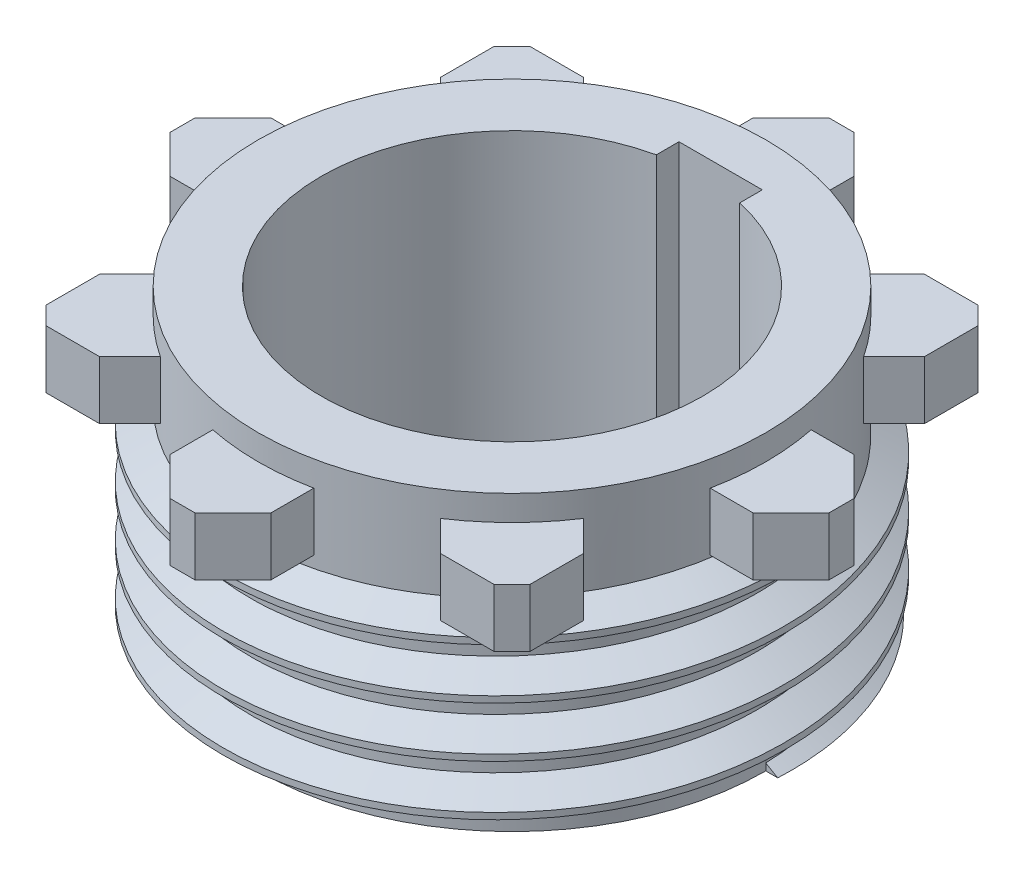
SolidWorks part; units mm, degrees
ref_plane "Alzado" through (0, 0, 0) normal (0, 0, 1) x (1, 0, 0)
ref_plane "Planta" through (0, 0, 0) normal (0, 1, 0) x (1, 0, 0)
ref_plane "Vista lateral" through (0, 0, 0) normal (1, 0, 0) x (0, 0, -1)
sketch "Croquis1" plane through (0, 0, 0) normal (0, 1, 0) x (1, 0, 0)
  line L0 (0, 10.05) -> (0, -10.05) construction
  line L1 (0, 8.263) -> (0, -7.437) construction
  line L2 (-1.65, 8.263) -> (1.65, 8.263)
  line L3 (-1.65, 8.263) -> (-1.65, 7.3675)
  line L5 (1.65, 8.263) -> (1.65, 7.3675)
  circle A0 centre (0, 0) radius 10.05
  arc A1 (-1.65, 7.3675) -> (1.65, 7.3675) centre (0, 0) ccw
  dimension "D1" = 15.1
  dimension "D2" = 2.5
  dimension "D3" = 1.65
  dimension "D4" = 1.65
  dimension "D5" = 15.7
  dimension "D6" = 0.8955
extrude "Saliente-Extruir2" add sketch "Croquis1" along normal blind 11.6
ref_plane "Plano1" through (10.05, 0, 0) normal (1, 0, 0) x (0, 0, -1)
sketch "Croquis3" plane through (10.05, 0, 0) normal (1, 0, 0) x (0, 0, -1)
  line L0 (0, 11.6) -> (0, 0) construction
  line L1 (10.05, 11.6) -> (-10.05, 11.6) construction
  line L2 (7.3675, 11.6) -> (-7.55, 11.6) construction
  line L3 (-2, 10.6) -> (2, 10.6)
  line L4 (-2, 10.6) -> (-2, 8.3)
  line L5 (-2, 8.3) -> (2, 8.3)
  line L6 (2, 10.6) -> (2, 8.3)
  dimension "D1" = 2
  dimension "D2" = 2
  dimension "D3" = 2.3
  dimension "D4" = 1
extrude "Saliente-Extruir3" add sketch "Croquis3" against normal blind 1
sketch "Croquis22" plane through (10.05, 0, 0) normal (1, 0, 0) x (0, 0, -1)
  line L1 (-2, 10.6) -> (2, 10.6)
  line L2 (-2, 10.6) -> (-2, 8.3)
  line L3 (-2, 8.3) -> (2, 8.3)
  line L4 (2, 10.6) -> (2, 8.3)
extrude "Saliente-Extruir4" add sketch "Croquis22" along normal blind 3
chamfer "Chaflán1" distance 1.5 angle 45 2 edges at (13.05, 9.45, -2) (13.05, 9.45, 2)
pattern_circular "MatrizC7" count 8 over 360 about axis through (0, 11.6, 0) along (0, -1, 0) of "Chaflán1", "Saliente-Extruir4", "Saliente-Extruir3"
thread "Rosca2" pitch 2 method extrude profile "Perfil de rosca3" start angle 0, offset 1.2, length 0, pitch 2, diameter 20.1
ref_plane "Plano4" through (10.05, -1.2, 0) normal (0, 0, 1) x (1, 0, 0)
sketch "Perfil de rosca3" plane through (10.05, -1.2, 0) normal (0, 0, 1) x (1, 0, 0)
  line L0 (0, 0) -> (0, 2) construction
  line L1 (0, 0) -> (1.06, 0.612)
  line L2 (1.06, 0.612) -> (1.06, 0.862)
  line L3 (1.06, 0.862) -> (0, 1.474)
  line L4 (1.06, 0.737) -> (0, 0.737) construction
  line L11 (0, 0) -> (0, 1.474)
  point P2 (0, 0)
  dimension "Pitch" = 2
  dimension "Profile_Angle" = 60
  dimension "Profile_Land" = 0.25
  dimension "Profile_Height" = 1.06
sketch "Croquis31" plane through (0, 0, 0) normal (0, -1, 0) x (1, 0, 0)
  circle A0 centre (0, 0) radius 13.7866
extrude "Cortar-Extruir1" cut sketch "Croquis31" along normal blind 2
